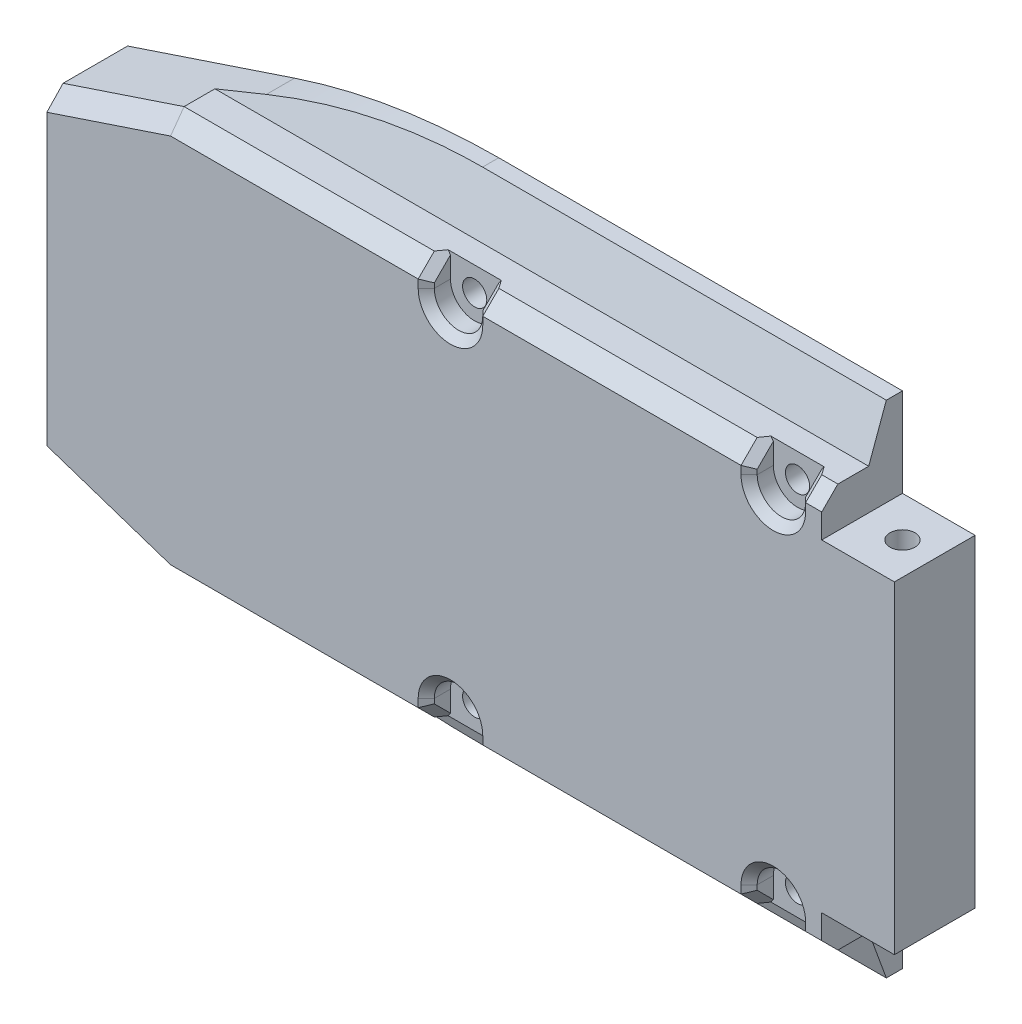
SolidWorks part; units mm, degrees
material "ABS"
ref_plane "Ebene vorne" through (0, 0, 0) normal (0, 0, 1) x (1, 0, 0)
ref_plane "Ebene oben" through (0, 0, 0) normal (0, 1, 0) x (1, 0, 0)
ref_plane "Ebene rechts" through (0, 0, 0) normal (1, 0, 0) x (0, 0, -1)
sketch "Skizze2" plane through (0, 0, 0) normal (0, 0, 1) x (1, 0, 0)
  line L0 (-151.7782, 0) -> (154.8922, 0) construction
  line L1 (0, 106.9611) -> (0, -93.0562) construction
  line L2 (0, 25) -> (-90, 25)
  line L3 (-90, 25) -> (-105, 20)
  line L4 (-105, 20) -> (-105, 11)
  line L5 (-105, 11) -> (-98, 11)
  line L6 (-95, 8) -> (-95, -8)
  line L7 (0, 25) -> (0, -25)
  line L8 (-105, -11) -> (-98, -11)
  line L9 (-105, -20) -> (-105, -11)
  line L10 (-90, -25) -> (-105, -20)
  line L11 (0, -25) -> (-90, -25)
  arc A0 (-98, -11) -> (-95, -8) centre (-98, -8) ccw
  arc A1 (-95, 8) -> (-98, 11) centre (-98, 8) ccw
  point P13 (0, 0)
  point P14 (-95, 0)
  point P19 (-95, -11)
  point P22 (-95, 11)
  dimension "D7" = 3
  dimension "D1" = 105
  dimension "D2" = 50
  dimension "D3" = 40
  dimension "D4" = 15
  dimension "D5" = 22
  dimension "D6" = 10
extrude "Aufsatz-Linear austragen1" add sketch "Skizze2" along normal blind 5 and the other way blind 5
hole_wizard "Ø3.1 (3.1) Durchmesser Bohrung1" positions "Skizze4" profile "Skizze3" hole size "Ø3.1" standard "ANSI Metrisch"
sketch "Skizze4" plane through (-105, 0, 0) normal (-1, 0, 0) x (0, 0, 1)
  line L0 (0, 37.8153) -> (0, -33.0973) construction
  line L3 (-22.117, 0) -> (22.0161, 0) construction
  point P0 (0, 15)
  point P14 (0, -15)
  dimension "D1" = 30
sketch "Skizze3" plane through (-105, 15, 0) normal (0, 1, 0) x (0, 0, 1)
  line L0 (0, 0) -> (0, 8.9313)
  line L1 (0, 8.9313) -> (1.55, 8)
  line L2 (1.55, 8) -> (1.55, 0)
  line L5 (1.55, 0) -> (0, 0)
  line L10 (0, 8.9313) -> (-1.55, 8) construction
  line L11 (0, -6.35) -> (0, 107.95) construction
  dimension "Bohrerdurchmesser" = 3.1
  dimension "Bohrungstiefe" = 8
  dimension "Spitzenwinkel" = 118
sketch "Skizze5" plane through (0, 0, 0) normal (0, 0, 1) x (1, 0, 0)
  line L0 (-134.3407, 0) -> (33.9152, 0) construction
  line L1 (0, 49.9151) -> (0, -37.4044) construction
  circle A0 centre (-55, 22) radius 1.5
  circle A1 centre (-15, 22) radius 1.5
  circle A2 centre (-15, -22) radius 1.5
  circle A3 centre (-55, -22) radius 1.5
  dimension "D1" = 3
  dimension "D2" = 40
  dimension "D3" = 15
  dimension "D4" = 22
extrude "Schnitt-Linear austragen1" cut sketch "Skizze5" against normal through all and the other way through all
sketch "Skizze6" plane through (0, 0, 5) normal (0, 0, 1) x (1, 0, 0)
  line L0 (-55, 22) -> (-55, 29.2626) construction
  line L1 (-58, 22) -> (-58, 29.2626)
  line L2 (-52, 22) -> (-52, 29.2626)
  line L3 (-15, 22) -> (-15, 29.2626) construction
  line L4 (-18, 22) -> (-18, 29.2626)
  line L5 (-12, 22) -> (-12, 29.2626)
  line L6 (-55, -22) -> (-55, -29.7807) construction
  line L7 (-52, -22) -> (-52, -29.7807)
  line L8 (-58, -22) -> (-58, -29.7807)
  line L9 (-15, -22) -> (-15, -30.8486) construction
  line L10 (-12, -22) -> (-12, -30.8486)
  line L11 (-18, -22) -> (-18, -30.8486)
  arc A4 (-58, 22) -> (-52, 22) centre (-55, 22) ccw
  arc A5 (-52, 29.2626) -> (-58, 29.2626) centre (-55, 29.2626) ccw
  arc A6 (-18, 22) -> (-12, 22) centre (-15, 22) ccw
  arc A7 (-12, 29.2626) -> (-18, 29.2626) centre (-15, 29.2626) ccw
  arc A8 (-52, -22) -> (-58, -22) centre (-55, -22) ccw
  arc A9 (-58, -29.7807) -> (-52, -29.7807) centre (-55, -29.7807) ccw
  arc A10 (-12, -22) -> (-18, -22) centre (-15, -22) ccw
  arc A11 (-18, -30.8486) -> (-12, -30.8486) centre (-15, -30.8486) ccw
  point P6 (-15, 25.6313)
  point P12 (-55, 25.6313)
  point P19 (-55, -25.8903)
  point P28 (-15, -26.4243)
  dimension "D1" = 3
extrude "Schnitt-Linear austragen2" cut sketch "Skizze6" against normal blind 3
sketch "Skizze7" plane through (0, 0, 5) normal (0, 0, 1) x (1, 0, 0)
  line L0 (-130.6386, 0) -> (13.2343, 0) construction
  line L1 (0, 46.5959) -> (0, -35.1065) construction
  line L2 (0, 25) -> (-9, 25)
  line L3 (0, 25) -> (-12, 25) construction
  line L4 (-9, 25) -> (-9, 20)
  line L5 (-9, 20) -> (0, 20)
  line L6 (0, 20) -> (0, 25)
  line L7 (0, -20) -> (0, -25)
  line L8 (-9, -20) -> (0, -20)
  line L9 (-9, -25) -> (-9, -20)
  line L10 (0, -25) -> (-9, -25)
  dimension "D1" = 5
  dimension "D2" = 9
extrude "Schnitt-Linear austragen3" cut sketch "Skizze7" against normal through all and the other way through all
sketch "Skizze8" plane through (0, 0, 0) normal (0, 0, 1) x (1, 0, 0)
  line L0 (-143.7875, 0) -> (29.5748, 0) construction
  line L1 (0, 40.8512) -> (0, -33.9576) construction
  line L17 (-55, 30.597) -> (-55, -26.6464) construction
  line L18 (-51, -22) -> (-19, -22)
  line L19 (-56, 18.127) -> (-56, -18.127)
  line L20 (-54, 18.127) -> (-54, -18.127)
  line L21 (-59, -22) -> (-89.5132, -22)
  line L22 (-89.5132, -22) -> (-93, -20.8377)
  line L23 (-93, -20.8377) -> (-93, 20.8377)
  line L24 (-90, -25) -> (-58, -25) construction
  line L25 (-105, -20) -> (-90, -25) construction
  line L26 (-95, 8) -> (-95, -8) construction
  line L27 (-89.5132, 22) -> (-93, 20.8377)
  line L28 (-59, 22) -> (-89.5132, 22)
  line L29 (-51, 22) -> (-19, 22)
  line L30 (-15, -18) -> (-7, -18)
  line L31 (-7, -18) -> (-7, 18)
  line L32 (-15, 18) -> (-7, 18)
  arc A6 (-56, -18.127) -> (-59, -22) centre (-55, -22) ccw
  arc A7 (-54, -18.127) -> (-51, -22) centre (-55, -22) cw
  arc A8 (-54, 18.127) -> (-51, 22) centre (-55, 22) ccw
  arc A9 (-56, 18.127) -> (-59, 22) centre (-55, 22) cw
  arc A10 (-19, -22) -> (-15, -18) centre (-15, -22) cw
  arc A11 (-19, 22) -> (-15, 18) centre (-15, 22) ccw
  point P16 (-56, 0)
  point P29 (-93, 0)
  point P30 (-54, 0)
  point P41 (-7, 0)
  dimension "D3" = 4
  dimension "D1" = 2
  dimension "D2" = 3
  dimension "D4" = 2
  dimension "D5" = 3
  dimension "D6" = 7
extrude "Schnitt-Linear austragen4" cut sketch "Skizze8" against normal through all and the other way blind 4
sketch "Skizze9" plane through (0, 0, -5) normal (0, 0, -1) x (-1, 0, 0)
  line L0 (-28.3161, 0) -> (120.4033, 0) construction
  line L1 (0, 48.4649) -> (0, -32.3525) construction
  line L2 (9, 25) -> (9, 31)
  line L3 (9, 31) -> (72, 31)
  line L7 (9, 25) -> (90, 25)
  line L8 (9, -25) -> (90, -25)
  line L11 (9, -31) -> (72, -31)
  line L12 (9, -25) -> (9, -31)
  line L13 (72, 31) -> (90, 25)
  line L14 (72, -31) -> (90, -25)
  line L15 (90, 25) -> (105, 20) construction
  dimension "D1" = 6
extrude "Aufsatz-Linear austragen2" add sketch "Skizze9" against normal blind 2
hole_wizard "Ø3.1 (3.1) Durchmesser Bohrung2" positions "Skizze11" profile "Skizze10" hole size "Ø3.1" standard "ANSI Metrisch"
sketch "Skizze11" plane through (0, 20, 0) normal (0, 1, 0) x (1, 0, 0)
  line L0 (14.2177, 0) -> (-26.5383, 0) construction
  point P0 (-4, 0)
  dimension "D1" = 4
sketch "Skizze10" plane through (-4, 20, 0) normal (1, 0, 0) x (0, 0, 1)
  line L0 (0, 0) -> (0, 10.9313)
  line L1 (0, 10.9313) -> (1.55, 10)
  line L2 (1.55, 10) -> (1.55, 0)
  line L5 (1.55, 0) -> (0, 0)
  line L10 (0, 10.9313) -> (-1.55, 10) construction
  line L11 (0, -6.35) -> (0, 107.95) construction
  dimension "Bohrerdurchmesser" = 3.1
  dimension "Bohrungstiefe" = 10
  dimension "Spitzenwinkel" = 118
mirror "Spiegeln1" about plane through (0, 0, 0) normal (0, 1, 0) of "Ø3.1 (3.1) Durchmesser Bohrung2"
chamfer "Fase1" distance 6 angle 20 1 edges at (-49.5, 25, -3) first distance on face at (-45, 28, -3)
chamfer "Fase2" distance 6 angle 20 1 edges at (-49.5, -25, -3) first distance on face at (-45, -28, -3)
fillet "Verrundung1" radius 80 2 edges at (-72, 31, -4) (-72, -31, -4)
fillet "Verrundung2" radius 2 14 edges at (-7, 18, -0.5) (-19, 22, -0.5) (-51, 22, -0.5) (-54, 18.127, -0.5) (-56, 18.127, -0.5) (-59, 22, -0.5) (-93, 20.8377, -0.5) (-93, -20.8377, -0.5) (-59, -22, -0.5) (-56, -18.127, -0.5) (-54, -18.127, -0.5) (-51, -22, -0.5) (-19, -22, -0.5) (-7, -18, -0.5)
sketch "Skizze12" plane through (0, 0, 5) normal (0, 0, 1) x (1, 0, 0)
  line L0 (-110.4008, 0) -> (7.7355, 0) construction
  line L1 (0, 42.6084) -> (0, -37.939) construction
  line L2 (-105, 11) -> (-105, -11)
  line L3 (-105, -11) -> (-95, -11)
  line L4 (-95, -11) -> (-95, 11)
  line L5 (-95, 11) -> (-105, 11)
  line L6 (-105, 20) -> (-105, 11) construction
  line L7 (-95, 8) -> (-95, -8) construction
extrude "Aufsatz-Linear austragen3" add sketch "Skizze12" against normal blind 1
chamfer "Fase3" distance 2 angle 45 8 edges at (-10.5, -25, 5) (-35, -25, 5) (-74, -25, 5) (-97.5, -22.5, 5) (-10.5, 25, 5) (-35, 25, 5) (-74, 25, 5) (-97.5, 22.5, 5)
fillet "Verrundung3" [suppressed] radius 1.5
sketch "Skizze13" plane through (0, 0, -5) normal (0, 0, -1) x (-1, 0, 0)
  line L0 (4, 10) -> (4, -10) construction
  line L1 (5.5, 10) -> (5.5, -10)
  line L2 (2.5, 10) -> (2.5, -10)
  line L3 (-14.13, 0) -> (38.0816, 0) construction
  arc A0 (5.5, 10) -> (2.5, 10) centre (4, 10) ccw
  arc A1 (2.5, -10) -> (5.5, -10) centre (4, -10) ccw
  point P4 (4, 0)
  dimension "D1" = 3
  dimension "D2" = 4
  dimension "D3" = 20
extrude "Schnitt-Linear austragen5" cut sketch "Skizze13" against normal up to surface (9 mm away) up to face at (-30.8946, 0, 4)
chamfer "Fase4" distance 1 angle 45 20 edges at (-12, -24, 4) (-18, -24, 4) (-12, -22.5, 5) (-18, -22.5, 5) (-15, -19, 5) (-58, 24, 4) (-52, 24, 4) (-58, 22.5, 5) (-52, 22.5, 5) (-55, 19, 5) (-18, 24, 4) (-12, 24, 4) (-18, 22.5, 5) (-12, 22.5, 5) (-15, 19, 5) (-52, -22.5, 5) (-58, -22.5, 5) (-55, -19, 5) (-58, -24, 4) (-52, -24, 4)
ref_axis "Achse1" through (-110.25, 0, 0) along (1, 0, 0)
ref_axis "Achse2" through (0, 0, -5.5) along (0, 0, 1)
ref_axis "Achse3" through (0, 34.1, 0) along (0, -1, 0)
